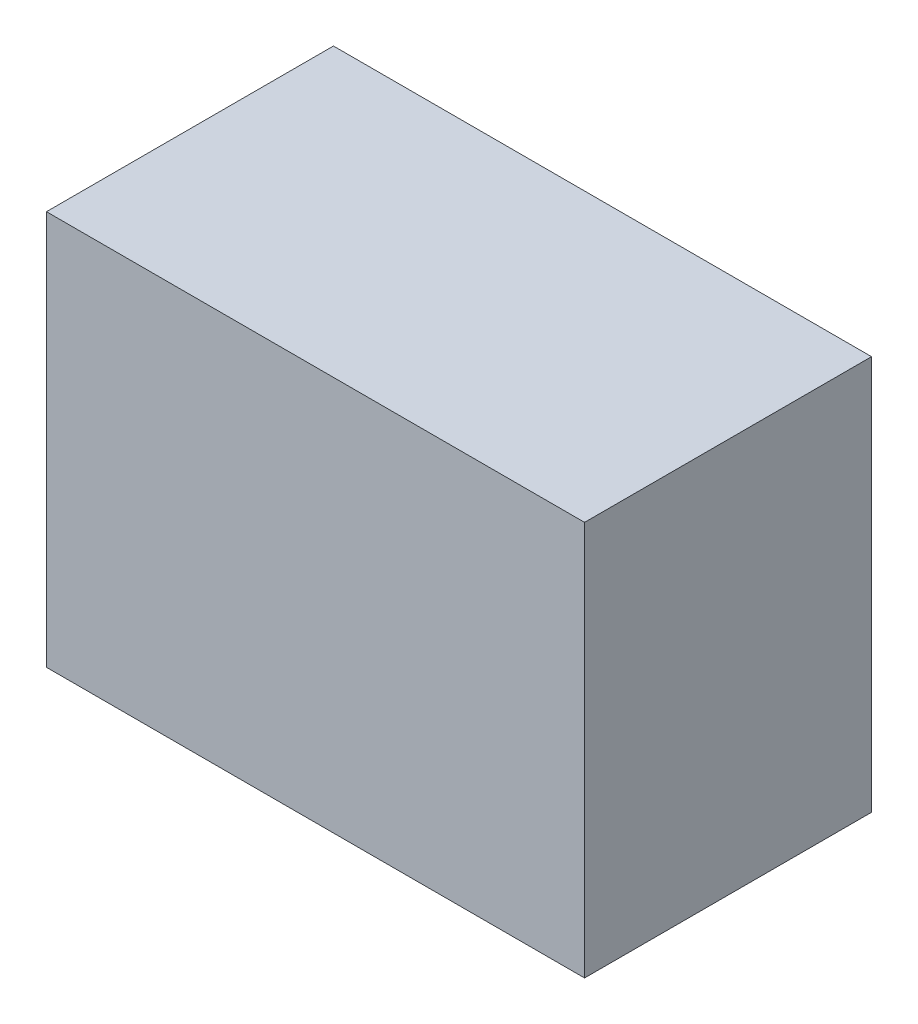
SolidWorks part; units mm, degrees
ref_plane "Front Plane" through (0, 0, 0) normal (0, 0, 1) x (1, 0, 0)
ref_plane "Top Plane" through (0, 0, 0) normal (0, 1, 0) x (1, 0, 0)
ref_plane "Right Plane" through (0, 0, 0) normal (1, 0, 0) x (0, 0, -1)
sketch "SK Pump body" plane through (0, 0, 0) normal (0, 1, 0) x (1, 0, 0)
  line L1 (0, 24) -> (45, 24)
  line L2 (0, 24) -> (0, 0)
  line L3 (0, 0) -> (45, 0)
  line L4 (45, 24) -> (45, 0)
extrude "Pump body" add sketch "SK Pump body" along normal blind 33 separate body
sketch "SK Outlet nozzle" plane through (0, 0, 0) normal (0, 1, 0) x (1, 0, 0)
  circle A0 centre (38, 12) radius 3.75
extrude "Outlet nozzle" [suppressed] add sketch "SK Outlet nozzle" along normal blind 12 from offset 33 separate body
sketch "SK Inlet" plane through (0, 0, 0) normal (1, 0, 0) x (0, 0, -1)
  circle A0 centre (12, 9) radius 4
extrude "Inlet" add sketch "SK Inlet" along normal blind 2 from offset 2 separate body offset against normal yes
sketch "SK Lead red" plane through (0, 0, 0) normal (0, 1, 0) x (1, 0, 0)
  circle A0 centre (6, 9) radius 0.8
extrude "Lead red" [suppressed] add sketch "SK Lead red" along normal blind 17 from offset 33 separate body
sketch "SK Lead black" plane through (0, 0, 0) normal (0, 1, 0) x (1, 0, 0)
  circle A0 centre (6, 15) radius 0.8
extrude "Lead black" [suppressed] add sketch "SK Lead black" along normal blind 17 from offset 33 separate body
